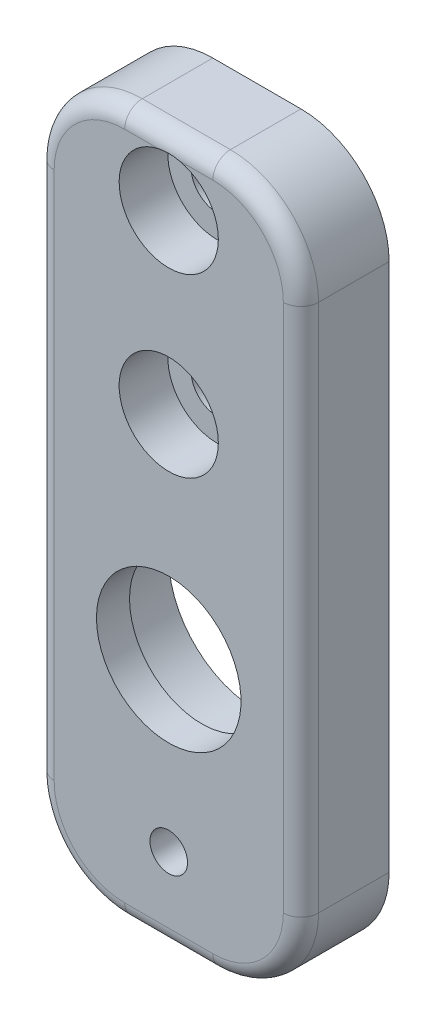
SolidWorks part; units mm, degrees
material "6061 Alloy"
ref_plane "Front Plane" through (0, 0, 0) normal (0, 0, 1) x (1, 0, 0)
ref_plane "Top Plane" through (0, 0, 0) normal (0, 1, 0) x (1, 0, 0)
ref_plane "Right Plane" through (0, 0, 0) normal (1, 0, 0) x (0, 0, -1)
sketch "Sketch1" plane through (0, 0, 0) normal (1, 0, 0) x (0, 0, -1)
  line L0 (0, 0) -> (0, 50.8)
  line L1 (0, 50.8) -> (6.35, 50.8)
  line L2 (6.35, 50.8) -> (6.35, 0)
  line L3 (0, 0) -> (6.35, 0)
  dimension "D1" = 50.8
  dimension "D2" = 6.35
extrude "Body" add sketch "Sketch1" along normal blind 19.05
sketch "Sketch2" plane through (0, 0, -6.35) normal (0, 0, -1) x (-1, 0, 0)
  line L0 (-9.525, 0) -> (-9.525, 18.034) construction
  line L1 (-19.05, 0) -> (0, 0) construction
  circle A0 centre (-9.525, 18.034) radius 6.35
  circle A1 centre (-9.525, 18.034) radius 5.207
  dimension "D1" = 12.7
  dimension "D3" = 10.414
  dimension "D2" = 18.034
extrude "Pitch Axle Opening" cut sketch "Sketch2" against normal blind 6.35 contours A1 region at (9.525, 18.034, -6.35)
hole_wizard "CBORE for #6 Socket Head Cap Screw1" positions "Sketch4" profile "Sketch3" counterbore size "#6" standard "Ansi Inch" end condition through all
sketch "Sketch4" plane through (0, 0, 0) normal (0, 0, 1) x (1, 0, 0)
  line L0 (0, 50.8) -> (19.05, 50.8)
  line L1 (9.525, 50.8) -> (9.525, 0) construction
  line L5 (0, 46.0375) -> (19.05, 46.0375) construction
  line L6 (0, 33.3375) -> (19.05, 33.3375) construction
  line L7 (19.05, 0) -> (0, 0) construction
  line L8 (19.05, 50.8) -> (19.05, 0) construction
  line L9 (0, 50.8) -> (0, 0) construction
  circle A0 centre (9.525, 18.034) radius 5.207 construction
  point P0 (9.525, 46.0375)
  point P22 (9.525, 33.3375)
  dimension "D1" = 4.7625
  dimension "D2" = 12.7
sketch "Sketch3" plane through (9.525, 46.0375, 0) normal (1, 0, 0) x (0, -1, 0)
  line L0 (0, 0) -> (0, 6.35)
  line L1 (0, 6.35) -> (1.8987, 6.35)
  line L3 (1.8987, 6.35) -> (1.8986, 3.5052)
  line L4 (1.8986, 3.5052) -> (3.5725, 3.5052)
  line L5 (3.5725, 3.5052) -> (3.5725, 0)
  line L7 (3.5725, 0) -> (0, 0)
  line L11 (0, -6.35) -> (0, 107.95) construction
  dimension "Thru Hole Dia." = 3.7973
  dimension "Thru Hole Depth" = 6.35
  dimension "C'Bore Dia." = 7.145
  dimension "C'Bore Depth" = 3.5052
hole_wizard "#6-32 Tapped Hole1" positions "3DSketch1" profile "Sketch5" tap size "#6-32" standard "Ansi Inch"
sketch3d "3DSketch1"
  line L0 (9.525, 50.8, 0) -> (9.525, 0, 0) construction
  line L4 (0, 6.034, 0) -> (19.05, 6.034, 0) construction
  line L6 (19.05, 0, 0) -> (0, 0, 0) construction
  line L7 (19.05, 50.8, 0) -> (0, 50.8, 0) construction
  line L8 (19.05, 50.8, 0) -> (19.05, 0, 0) construction
  line L9 (0, 50.8, 0) -> (0, 0, 0) construction
  circle A1 centre (9.525, 18.034, 0) radius 5.207 construction
  point P0 (9.525, 6.034, 0)
  point P34 (9.525, 18.034, -5.207)
  dimension "D1" = 12
sketch "Sketch5" plane through (9.525, 6.034, 0) normal (1, 0, 0) x (0, -1, 0)
  line L0 (0, 0) -> (0, 5.8927)
  line L1 (0, 5.8927) -> (1.3525, 5.08)
  line L2 (1.3525, 5.08) -> (1.3525, 0)
  line L5 (1.3525, 0) -> (0, 0)
  line L10 (0, 5.8927) -> (-1.3526, 5.08) construction
  line L11 (0, -6.35) -> (0, 107.95) construction
  dimension "Tap Drill Dia." = 2.7051
  dimension "Tap Drill Depth" = 5.08
  dimension "Drill Angle" = 118
cosmetic thread "Hole Thread1" parameters "D1"=5.08, "D2"=3.5052
extrude "Pitch Bearing Recess" cut sketch "Sketch2<3>" against normal blind 3.9675
sketch "Sketch2<3>" plane through (0, 0, -6.35) normal (0, 0, -1) x (-1, 0, 0) same geometry as "Sketch2"
fillet "Fillet1" radius 6.35 4 edges at (0, 50.8, -3.175) (19.05, 50.8, -3.175) (0, 0, -3.175) (19.05, 0, -3.175)
fillet "Fillet2" radius 1.27 8 edges at (17.1901, 48.9401, 0) (9.525, 50.8, 0) (1.8599, 48.9401, 0) (0, 25.4, 0) (1.8599, 1.8599, 0) (9.525, 0, 0) (17.1901, 1.8599, 0) (19.05, 25.4, 0)
